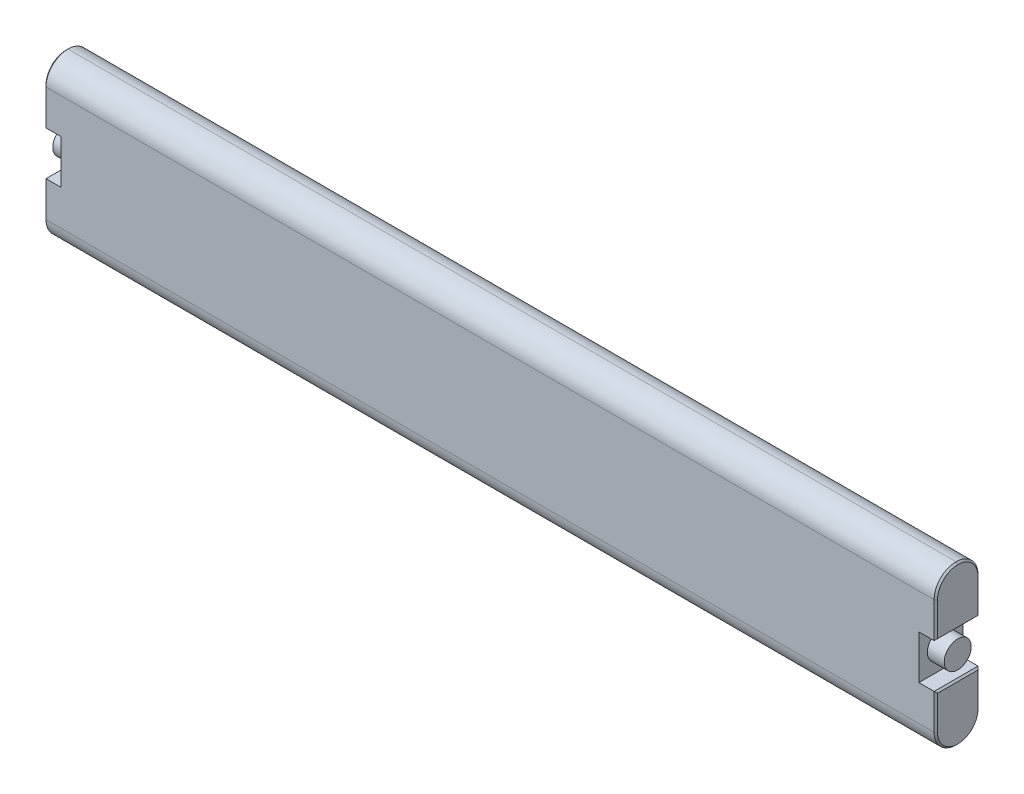
SolidWorks part; units mm, degrees
material "ABS"
ref_plane "Front Plane" through (0, 0, 0) normal (0, 0, 1) x (1, 0, 0)
ref_plane "Top Plane" through (0, 0, 0) normal (0, 1, 0) x (1, 0, 0)
ref_plane "Right Plane" through (0, 0, 0) normal (1, 0, 0) x (0, 0, -1)
sketch "Sketch1" plane through (0, 0, 0) normal (0, 0, 1) x (1, 0, 0)
  line L12 (-102.4222, 0) -> (104.1541, 0) construction
  line L13 (0, 61.1513) -> (0, -79.2086) construction
  line L24 (0, -11.75) -> (-66, -11.75)
  line L29 (-66, -11.75) -> (-66, -3.25)
  line L30 (-66, -3.25) -> (-63.5, -3.25)
  line L33 (-63.5, 3.25) -> (-66, 3.25)
  line L34 (-66, 3.25) -> (-66, 11.75)
  line L35 (-66, 11.75) -> (0, 11.75)
  line L36 (0, 11.75) -> (0, -11.75)
  line L37 (0, 0) -> (-76.2862, 0) construction
  line L38 (-63.5, 3.25) -> (-63.5, -3.25)
  point P6 (-63.5, 0)
  dimension "D1" = 66
  dimension "D2" = 23.5
  dimension "D3" = 6.5
  dimension "D4" = 2.5
extrude "Boss-Extrude1" add sketch "Sketch1" along normal blind 6.5
sketch "Sketch2" plane through (-63.5, 0, 0) normal (-1, 0, 0) x (0, 0, 1)
  line L0 (0, 0) -> (6.5, 0) construction
  line L1 (6.5, 3.25) -> (6.5, -3.25) construction
  line L2 (3.25, 3.25) -> (3.25, -3.25) construction
  line L3 (6.5, 3.25) -> (0, 3.25) construction
  line L4 (6.5, -3.25) -> (0, -3.25) construction
  circle A0 centre (3.25, 0) radius 2
  dimension "D1" = 4
extrude "Boss-Extrude2" add sketch "Sketch2" along normal blind 2.5
mirror "Mirror1" about plane through (0, 0, 0) normal (1, 0, 0) of "Boss-Extrude2", "Boss-Extrude1"
fillet "Fillet5" radius 3.25 4 edges at (0, -11.75, 0) (0, -11.75, 6.5) (0, 11.75, 6.5) (0, 11.75, 0)
chamfer "Chamfer1" distance 0.25 angle 45 20 edges at (66, -5.875, 6.5) (66, -3.25, 3.25) (66, -5.875, 0) (66, -10.7981, 0.9519) (66, -10.7981, 5.5481) (66, 5.875, 0) (66, 3.25, 3.25) (66, 5.875, 6.5) (66, 10.7981, 5.5481) (66, 10.7981, 0.9519) (-66, -3.25, 3.25) (-66, -5.875, 6.5) (-66, -10.7981, 5.5481) (-66, -10.7981, 0.9519) (-66, -5.875, 0) (-66, 3.25, 3.25) (-66, 5.875, 0) (-66, 10.7981, 0.9519) (-66, 10.7981, 5.5481) (-66, 5.875, 6.5)
